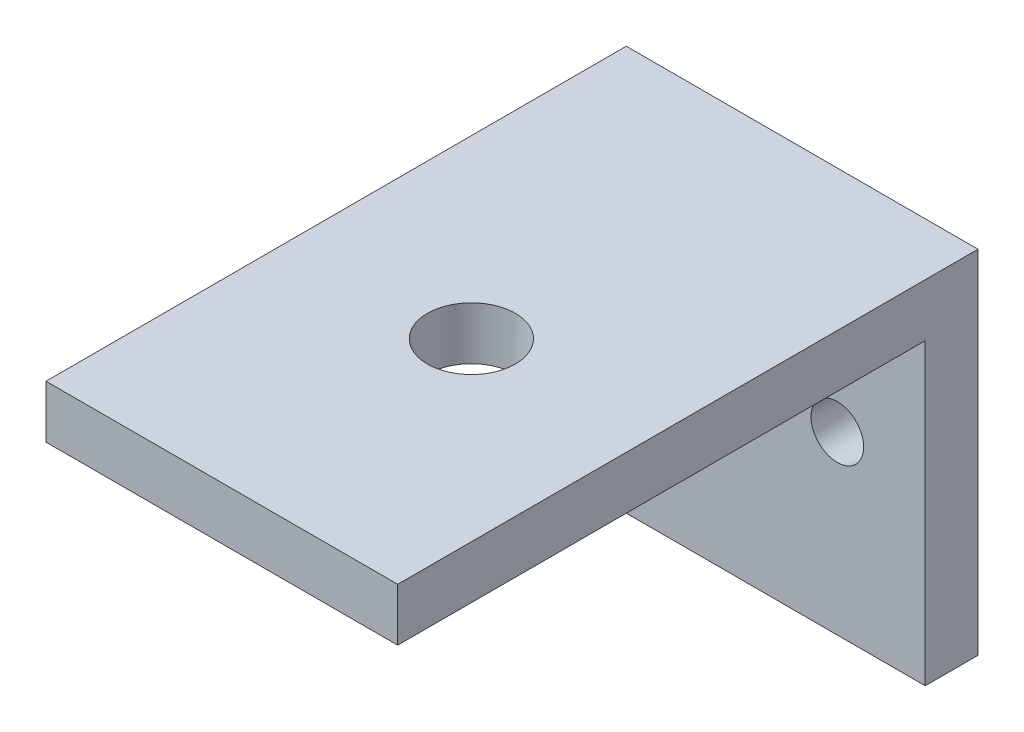
SolidWorks part; units mm, degrees
ref_plane "Front Plane" through (0, 0, 0) normal (0, 0, 1) x (1, 0, 0)
ref_plane "Top Plane" through (0, 0, 0) normal (0, 1, 0) x (1, 0, 0)
ref_plane "Right Plane" through (0, 0, 0) normal (1, 0, 0) x (0, 0, -1)
sketch "Sketch1" plane through (0, 0, 0) normal (0, 0, 1) x (1, 0, 0)
  line L1 (-10, 10) -> (10, 10)
  line L2 (-10, 10) -> (-10, -10)
  line L3 (-10, -10) -> (10, -10)
  line L4 (10, 10) -> (10, -10)
  line L5 (-10, 10) -> (10, -10) construction
  line L6 (-10, -10) -> (10, 10) construction
  point P0 (0, 0)
  dimension "D1" = 20
  dimension "D2" = 20
extrude "Boss-Extrude1" add sketch "Sketch1" along normal blind 3
sketch "Sketch2" plane through (0, 0, 3) normal (0, 0, 1) x (1, 0, 0)
  line L0 (10, -10) -> (10, 10) construction
  line L1 (-10, 10) -> (10, 10)
  line L2 (-10, 10) -> (-10, 7)
  line L3 (-10, 7) -> (10, 7)
  line L4 (10, 10) -> (10, 7)
  dimension "D1" = 3
extrude "Boss-Extrude2" add sketch "Sketch2" along normal blind 30
sketch "Sketch3" plane through (0, 0, 3) normal (0, 0, 1) x (1, 0, 0)
  line L0 (0, 10) -> (0, -10) construction
  line L2 (-10, -10) -> (10, -10) construction
  line L3 (-10, 0) -> (10, 0) construction
  line L6 (10, 10) -> (-10, 10) construction
  circle A0 centre (-5, 0) radius 1.5
  circle A1 centre (5, 0) radius 1.5
  dimension "D1" = 3
  dimension "D2" = 5
extrude "Cut-Extrude1" cut sketch "Sketch3" against normal blind 20
sketch "Sketch5" plane through (0, 10, 0) normal (0, 1, 0) x (1, 0, 0)
  line L1 (10, 0) -> (-10, 0) construction
  circle A0 centre (0, -18.81) radius 2.5
  dimension "D1" = 5
  dimension "D2" = 18.81
extrude "Cut-Extrude2" cut sketch "Sketch5" against normal blind 20
